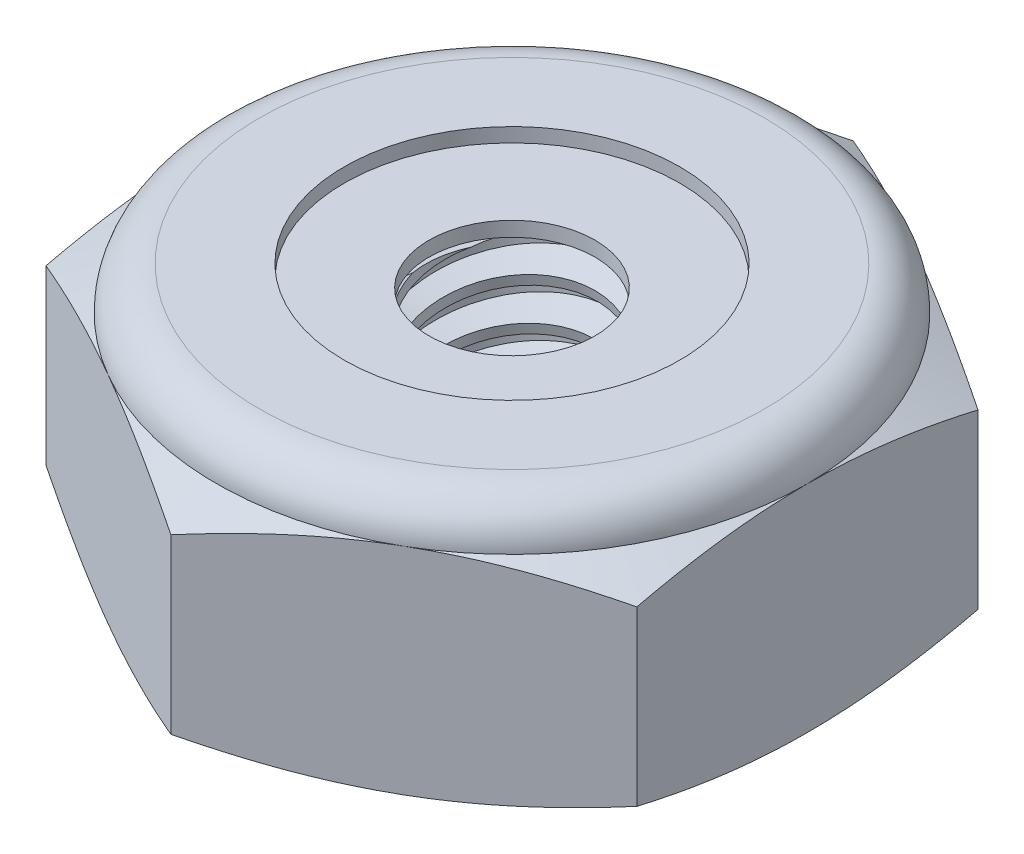
SolidWorks part; units mm, degrees
ref_plane "Front" through (0, 0, 0) normal (0, 0, 1) x (1, 0, 0)
ref_plane "Top" through (0, 0, 0) normal (0, 1, 0) x (1, 0, 0)
ref_plane "Right" through (0, 0, 0) normal (1, 0, 0) x (0, 0, -1)
sketch "Sketch1" plane through (0, 0, 0) normal (0, 1, 0) x (1, 0, 0)
  line L1 (0, 3.6662) -> (-3.175, 1.8331)
  line L2 (-3.175, 1.8331) -> (-3.175, -1.8331)
  line L3 (-3.175, -1.8331) -> (0, -3.6662)
  line L4 (0, -3.6662) -> (3.175, -1.8331)
  line L5 (3.175, -1.8331) -> (3.175, 1.8331)
  line L6 (3.175, 1.8331) -> (0, 3.6662)
  circle A0 centre (0, 0) radius 3.175 construction
  dimension "Hex Flats" = 6.35
extrude "Extrude1" add sketch "Sketch1" along normal blind 2.7781
sketch "Sketch2" plane through (0, 0, 0) normal (1, 0, 0) x (0, 0, -1)
  line L0 (-1.0922, 0) -> (-1.0922, 2.7781) construction
  line L1 (0, 0) -> (1.0922, 0)
  line L2 (0, 0) -> (0, 2.7781)
  line L3 (0, 2.7781) -> (1.0922, 2.7781)
  line L4 (1.0922, 0) -> (1.0922, 2.7781)
  line L5 (-1.8331, 2.7781) -> (1.8331, 2.7781) construction
  line L7 (0, -1.0922) -> (0, 0) construction
  dimension "Thread Dia" = 2.1844
revolve "Revolve1" add sketch "Sketch2" angle 360 about L7
sketch "Sketch3" plane through (0, 0, 0) normal (1, 0, 0) x (0, 0, -1)
  line L0 (1.0922, 2.7781) -> (-1.0922, 2.7781) construction
  line L1 (-1.0922, 2.7781) -> (-1.0922, 2.3246) construction
  line L2 (-1.0922, 2.3246) -> (1.0922, 2.7781) construction
  line L3 (1.0922, 2.7781) -> (1.1037, 2.7226) construction
  line L4 (1.1037, 2.7226) -> (1.1844, 2.334)
  line L5 (1.1844, 2.334) -> (0.9152, 2.4229)
  line L6 (0.9152, 2.4229) -> (0.8922, 2.5339)
  line L7 (0.8922, 2.5339) -> (1.1037, 2.7226)
  line L8 (0.9037, 2.4784) -> (1.1441, 2.5283) construction
  line L9 (1.0922, 2.7781) -> (1.0922, 2.5175) construction
  line L10 (1.0922, 2.5175) -> (-1.0922, 2.064) construction
  line L11 (-1.0922, 2.064) -> (-1.0922, 2.3246) construction
  line L12 (-0.1012, 2.7781) -> (0.1012, 1.8034) construction
  line L13 (-1.0922, 0) -> (-1.0922, 2.7781) construction
  line L14 (0, 2.7781) -> (1.0922, 2.7781) construction
  line L15 (1.0922, 0) -> (1.0922, 2.7781) construction
  point P13 (0, 2.2908)
  dimension "D1" = 0.0567
  dimension "D2" = 0.1134
  dimension "Thread Pitch" = 0.4536
  dimension "D4" = 60
  dimension "D5" = 0.4536
revolve "Cut-Revolve1" cut sketch "Sketch3" angle 360 about L12
pattern_linear "LPattern1" count 6 spacing 0.4536 along (0, -1, 0) count 2 spacing 0.4536 along (0, 1, 0) of "Cut-Revolve1"
sketch "Sketch4" plane through (0, 0, 0) normal (1, 0, 0) x (0, 0, -1)
  line L0 (0, 2.7781) -> (1.0922, 2.7781)
  line L1 (1.0922, 2.7781) -> (0.8922, 2.6848)
  line L2 (0.8922, 2.6848) -> (0.8922, 0.0933)
  line L3 (0.8922, 0.0933) -> (1.0922, 0)
  line L4 (1.0922, 0) -> (0, 0)
  line L5 (0, 0) -> (0, 2.7781)
  line L6 (1.0922, 0) -> (1.0922, 2.7781) construction
  line L7 (0, 2.7781) -> (1.0922, 2.7781) construction
  line L8 (0, 0) -> (1.0922, 0) construction
  line L9 (0, 0) -> (0, 2.7781) construction
  line L10 (0, 2.7781) -> (0, 2.9988) construction
  dimension "D1" = 25
revolve "Cut-Revolve2" cut sketch "Sketch4" angle 360 about L10
combine bodies "Combine1" operation type subtract main body 112 bodies to subtract 111
sketch "Sketch5" plane through (0, 0, 0) normal (1, 0, 0) x (0, 0, -1)
  line L0 (0, 0) -> (3.175, 0)
  line L1 (3.175, 0) -> (3.6662, 0.229)
  line L2 (3.6662, 0.229) -> (3.6662, 2.0861)
  line L3 (3.6662, 2.0861) -> (3.175, 2.3151)
  line L4 (2.712, 2.7781) -> (2.712, 4.0481)
  line L5 (2.712, 4.0481) -> (4.9362, 4.0481)
  line L6 (4.9362, 4.0481) -> (4.9362, -1.27)
  line L7 (4.9362, -1.27) -> (0, -1.27)
  line L8 (0, -1.27) -> (0, 0)
  line L9 (3.175, 2.3151) -> (3.175, 0) construction
  line L10 (0, 0) -> (1.0922, 0) construction
  line L13 (3.6662, 1.1576) -> (4.9362, 1.1576) construction
  line L14 (3.6662, 2.7781) -> (3.6662, 0) construction
  line L15 (0, 0) -> (0, 4.0481) construction
  line L20 (0, 4.0481) -> (2.712, 4.0481) construction
  line L22 (0, 2.7781) -> (1.0922, 2.7781) construction
  arc A0 (3.175, 2.3151) -> (2.712, 2.7781) centre (2.712, 2.3151) ccw
  dimension "D1" = 25
  dimension "D2" = 1.27
  dimension "D3" = 2.7781
  dimension "D4" = 0.463
revolve "Cut-Revolve3" cut sketch "Sketch5" angle 360 about L15
sketch "Sketch6" plane through (0, 0, 0) normal (1, 0, 0) x (0, 0, -1)
  line L0 (0, 2.3151) -> (3.0226, 2.3151)
  line L1 (2.712, 2.6257) -> (1.8021, 2.6257)
  line L2 (0, 4.0481) -> (0, 2.3151)
  line L3 (1.8021, 4.0481) -> (0, 4.0481)
  line L4 (0, 4.0481) -> (2.712, 4.0481) construction
  line L5 (0, 0) -> (0, 4.0481) construction
  line L6 (0, 4.0481) -> (0, 44.323) construction
  line L7 (1.8021, 2.6257) -> (1.8021, 4.0481)
  line L8 (2.712, 2.7781) -> (2.712, 2.6257) construction
  line L9 (1.8021, 2.6257) -> (0.8922, 2.6257) construction
  line L10 (0.8922, 2.6257) -> (0.8922, 2.6848) construction
  arc A0 (3.0226, 2.3151) -> (2.712, 2.6257) centre (2.712, 2.3151) ccw
  arc A1 (3.175, 2.3151) -> (2.712, 2.7781) centre (2.712, 2.3151) ccw construction
  dimension "D1" = 0.1524
revolve "Cut-Revolve4" cut sketch "Sketch6" angle 360 about L6
sketch "Sketch7" plane through (0, 0, 0) normal (1, 0, 0) x (0, 0, -1)
  line L0 (0.8922, 2.3913) -> (2.9337, 2.3913)
  line L1 (2.712, 2.5495) -> (0.8922, 2.5495)
  line L2 (0.8922, 2.5495) -> (0.8922, 2.3913)
  line L3 (0.8922, 2.3913) -> (0, 2.3913) construction
  line L4 (0, 2.3913) -> (0, 2.5495) construction
  line L5 (0, 2.5495) -> (0.8922, 2.5495) construction
  line L6 (0.8922, 2.3913) -> (0.8922, 2.3151) construction
  line L7 (0, 2.3151) -> (3.0226, 2.3151) construction
  line L8 (2.712, 2.5495) -> (2.712, 2.6257) construction
  arc A0 (2.9337, 2.3913) -> (2.712, 2.5495) centre (2.712, 2.3151) ccw
  arc A2 (3.0226, 2.3151) -> (2.712, 2.6257) centre (2.712, 2.3151) ccw construction
  dimension "D1" = 0.0762
revolve "Revolve2" add sketch "Sketch7" angle 360 about L4
equation "\"D1@Sketch3\"=\"Thread Pitch@Sketch3\"/8"
equation "\"D2@Sketch3\"=\"Thread Pitch@Sketch3\"/4"
equation "\"D5@Sketch3\"=\"Thread Pitch@Sketch3\""
equation "\"D4@LPattern1\"=\"Thread Pitch@Sketch3\""
equation "\"D3@LPattern1\"=\"Thread Pitch@Sketch3\""
equation "\"D1@LPattern1\"=\"Height@Extrude1\"/\"Thread Pitch@Sketch3\""
equation "\"D4@Sketch5\"=\"Height@Extrude1\"/6"
